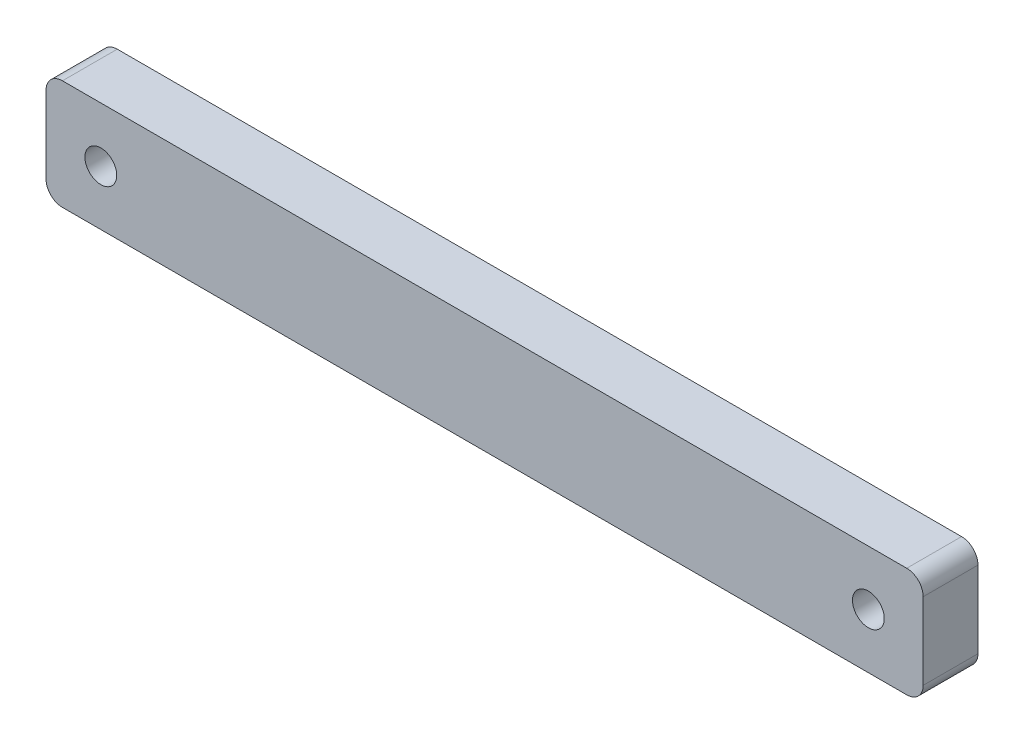
SolidWorks part; units mm, degrees
ref_plane "Front Plane" through (0, 0, 0) normal (0, 0, 1) x (1, 0, 0)
ref_plane "Top Plane" through (0, 0, 0) normal (0, 1, 0) x (1, 0, 0)
ref_plane "Right Plane" through (0, 0, 0) normal (1, 0, 0) x (0, 0, -1)
sketch "Sketch1" plane through (0, 0, 0) normal (0, 0, 1) x (1, 0, 0)
  line L1 (97.79, -12.7) -> (-97.79, -12.7)
  line L2 (101.6, -8.89) -> (101.6, 8.89)
  line L3 (97.79, 12.7) -> (-97.79, 12.7)
  line L4 (-101.6, -8.89) -> (-101.6, 8.89)
  line L5 (101.6, -12.7) -> (-101.6, 12.7) construction
  line L6 (101.6, 12.7) -> (-101.6, -12.7) construction
  arc A0 (101.6, 8.89) -> (97.79, 12.7) centre (97.79, 8.89) ccw
  arc A1 (97.79, -12.7) -> (101.6, -8.89) centre (97.79, -8.89) ccw
  arc A2 (-97.79, -12.7) -> (-101.6, -8.89) centre (-97.79, -8.89) cw
  arc A3 (-97.79, 12.7) -> (-101.6, 8.89) centre (-97.79, 8.89) ccw
  circle A4 centre (-88.9, 0) radius 3.683
  circle A5 centre (88.9, 0) radius 3.683
  point P0 (0, 0)
  dimension "D3" = 3.81
  dimension "D6" = 7.366
  dimension "D7" = 7.366
  dimension "D1" = 25.4
  dimension "D2" = 203.2
  dimension "D4" = 88.9
  dimension "D5" = 88.9
extrude "Boss-Extrude1" add sketch "Sketch1" along normal blind 12.7
sketch "Sketch2" plane through (0, 0, 0) normal (0, 0, -1) x (-1, 0, 0)
  circle A0 centre (-88.9, 0) radius 3.683
  circle A1 centre (88.9, 0) radius 3.683
extrude "Boss-Extrude2" add sketch "Sketch2" against normal blind 6.35
